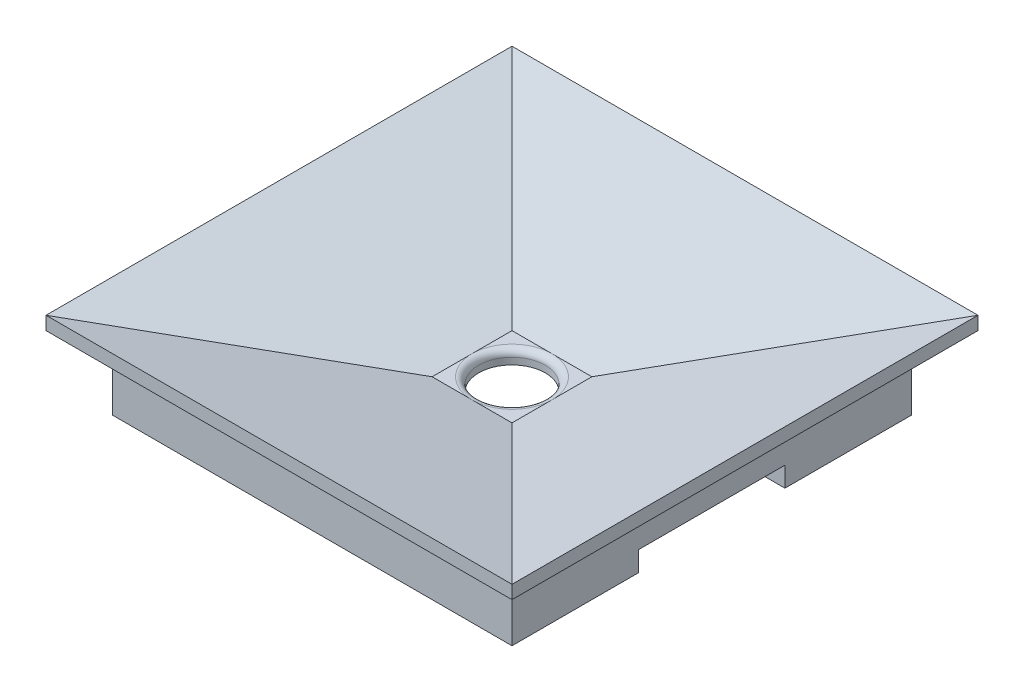
SolidWorks part; units mm, degrees
ref_plane "Front Plane" through (0, 0, 0) normal (0, 0, 1) x (1, 0, 0)
ref_plane "Top Plane" through (0, 0, 0) normal (0, 1, 0) x (1, 0, 0)
ref_plane "Right Plane" through (0, 0, 0) normal (1, 0, 0) x (0, 0, -1)
sketch "Sketch1" plane through (0, 0, 0) normal (0, 1, 0) x (1, 0, 0)
  line L1 (-30, -30) -> (30, -30)
  line L2 (-30, -30) -> (-30, 30)
  line L3 (-30, 30) -> (30, 30)
  line L4 (30, -30) -> (30, 30)
  line L5 (-30, -30) -> (30, 30) construction
  line L6 (-30, 30) -> (30, -30) construction
  point P0 (0, 0)
  dimension "D1" = 60
  dimension "D2" = 60
extrude "Boss-Extrude1" add sketch "Sketch1" along normal blind 6 contours L3 L4 L1 L2
sketch "Sketch2" plane through (0, 0, 0) normal (0, -1, 0) x (1, 0, 0)
  line L1 (14, 13.335) -> (-14, 13.335) construction
  line L2 (14, 13.335) -> (14, -13.335) construction
  line L3 (14, -13.335) -> (-14, -13.335) construction
  line L4 (-14, 13.335) -> (-14, -13.335) construction
  line L5 (14, 13.335) -> (-14, -13.335) construction
  line L6 (14, -13.335) -> (-14, 13.335) construction
  circle A0 centre (-14, -13.335) radius 0.925
  circle A1 centre (14, -13.335) radius 0.925
  circle A2 centre (14, 13.335) radius 0.925
  circle A3 centre (-14, 13.335) radius 0.925
  point P0 (0, 0)
  dimension "D3" = 1.85
  dimension "D1" = 26.67
  dimension "D2" = 28
sketch "Sketch3" plane through (0, 0, 0) normal (0, -1, 0) x (1, 0, 0)
  circle A0 centre (0, 0) radius 5
  dimension "D1" = 10
sketch "Sketch7" plane through (0, 6, 0) normal (0, 1, 0) x (1, 0, 0)
  line L0 (30, -30) -> (30, 30) construction
  line L1 (-28, 28) -> (28, 28)
  line L2 (-28, 28) -> (-28, -28)
  line L3 (-28, -28) -> (28, -28)
  line L4 (28, 28) -> (28, -28)
  line L5 (-28, 28) -> (28, -28) construction
  line L6 (-28, -28) -> (28, 28) construction
  line L7 (-30, -30) -> (30, -30) construction
  line L12 (-30, 30) -> (-30, -30)
  line L13 (-30, -30) -> (30, -30)
  line L14 (30, -30) -> (30, 30)
  line L15 (30, 30) -> (-30, 30)
  line L16 (-30, 30) -> (-30, -30)
  line L17 (-30, -30) -> (30, -30)
  line L18 (30, -30) -> (30, 30)
  line L19 (30, 30) -> (-30, 30)
  point P0 (0, 0)
  dimension "D1" = 2
  dimension "D2" = 2
  dimension "D3" = 0
extrude "Boss-Extrude4" add sketch "Sketch7" along normal blind 7
sketch "Sketch8" plane through (0, 13, 0) normal (0, 1, 0) x (1, 0, 0)
  line L1 (35, -35) -> (-35, -35)
  line L2 (35, -35) -> (35, 35)
  line L3 (35, 35) -> (-35, 35)
  line L4 (-35, -35) -> (-35, 35)
  line L5 (35, -35) -> (-35, 35) construction
  line L6 (35, 35) -> (-35, -35) construction
  line L10 (30, 30) -> (-30, 30)
  line L11 (-30, 30) -> (-30, -30)
  line L12 (-30, -30) -> (30, -30)
  line L13 (30, -30) -> (30, 30)
  line L14 (30, 30) -> (-30, 30)
  line L15 (-30, 30) -> (-30, -30)
  line L16 (-30, -30) -> (30, -30)
  line L17 (30, -30) -> (30, 30)
  point P0 (0, 0)
  dimension "D2" = 5
  dimension "D3" = 5
  dimension "D1" = 0
extrude "Boss-Extrude5" add sketch "Sketch8" against normal blind 2
sketch "Sketch12" plane through (0, 6, 0) normal (0, 1, 0) x (1, 0, 0)
  line L4 (-28, -28) -> (28, -28)
  line L5 (28, -28) -> (28, 28)
  line L6 (28, 28) -> (-28, 28)
  line L7 (-28, 28) -> (-28, -28)
  line L8 (-28, -28) -> (28, -28)
  line L9 (28, -28) -> (28, 28)
  line L10 (28, 28) -> (-28, 28)
  line L11 (-28, 28) -> (-28, -28)
  dimension "D1" = 0
extrude "Boss-Extrude10" add sketch "Sketch12" along normal up to surface (7 mm away) up to face at (0, 13, 0)
sketch "Sketch13" plane through (0, 13, 0) normal (0, 1, 0) x (1, 0, 0)
  line L1 (-6, 6) -> (6, 6)
  line L2 (-6, 6) -> (-6, -6)
  line L3 (-6, -6) -> (6, -6)
  line L4 (6, 6) -> (6, -6)
  line L5 (-6, 6) -> (6, -6) construction
  line L6 (-6, -6) -> (6, 6) construction
  point P0 (0, 0)
  dimension "D1" = 12
  dimension "D2" = 12
extrude "Cut-Extrude3" cut sketch "Sketch13" against normal offset from surface (8 mm away) 5 up to face at (0, 0, 0)
sketch "Sketch14" plane through (0, 13, 0) normal (0, 1, 0) x (1, 0, 0)
  line L4 (-35, 35) -> (-35, -35)
  line L5 (-35, -35) -> (35, -35)
  line L6 (35, -35) -> (35, 35)
  line L7 (35, 35) -> (-35, 35)
  line L8 (-35, 35) -> (-35, -35)
  line L9 (-35, -35) -> (35, -35)
  line L10 (35, -35) -> (35, 35)
  line L11 (35, 35) -> (-35, 35)
  dimension "D1" = 0
loft "Cut-Loft1" cut profiles "Sketch14" section face at (0, 5, 0) section "Sketch14" connector at (6, 5, 6) connector at (35, 13, 35)
extrude "Cut-Extrude4" cut sketch "Sketch3" against normal through all contours A0
extrude "Cut-Extrude5" cut sketch "Sketch2" against normal blind 3
sketch "Sketch15" plane through (0, 0, 0) normal (0, -1, 0) x (1, 0, 0)
  line L1 (11, -15.335) -> (-11, -15.335)
  line L2 (11, -15.335) -> (11, 15.335)
  line L3 (11, 15.335) -> (-11, 15.335)
  line L4 (-11, -15.335) -> (-11, 15.335)
  line L5 (11, -15.335) -> (-11, 15.335) construction
  line L6 (11, 15.335) -> (-11, -15.335) construction
  line L7 (15.335, -11) -> (-15.335, -11)
  line L8 (15.335, -11) -> (15.335, 11)
  line L9 (15.335, 11) -> (-15.335, 11)
  line L10 (-15.335, -11) -> (-15.335, 11)
  line L11 (15.335, -11) -> (-15.335, 11) construction
  line L12 (15.335, 11) -> (-15.335, -11) construction
  circle A0 centre (-14, -13.335) radius 0.925 construction
  point P0 (0, 0)
  point P6 (0, 0)
  circle M13 centre (0, 0) radius 5
  dimension "D1" = 3
  dimension "D2" = 2
extrude "Cut-Extrude6" cut sketch "Sketch15" against normal blind 3 contours L2 L7 L4 L1 | L2 L9 L4 L7 M13 | L10 L7 L4 L9 | L9 L2 L3 L4 | L8 L9 L2 L7
sketch "Sketch16" plane through (0, 0, 0) normal (0, -1, 0) x (1, 0, 0)
  line L0 (15.335, -11) -> (15.335, 11) construction
  line L1 (30, -11) -> (15.335, -11)
  line L2 (30, -11) -> (30, 11)
  line L3 (30, 11) -> (15.335, 11)
  line L4 (15.335, -11) -> (15.335, 11)
  line L5 (30, -11) -> (15.335, 11) construction
  line L6 (30, 11) -> (15.335, -11) construction
  line L7 (30, 30) -> (30, -30) construction
  point P0 (22.6675, 0)
extrude "Cut-Extrude7" cut sketch "Sketch16" against normal up to surface (3 mm away) up to face at (0, 3, 0)
fillet "Fillet1" radius 4 4 edges at (11, 1.5, -11) (11, 1.5, 11) (-11, 1.5, 11) (-11, 1.5, -11)
fillet "Fillet2" radius 1 1 edges at (0, 5, -5)
